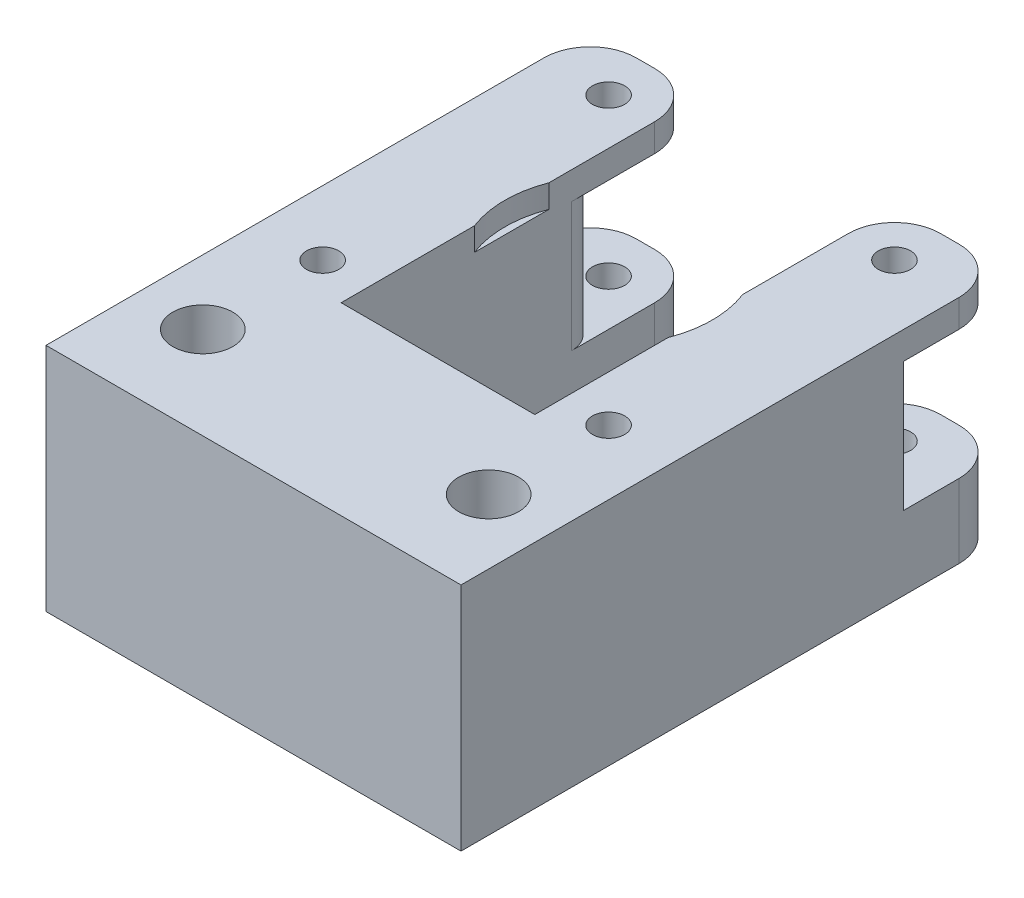
SolidWorks part; units mm, degrees
material "ABS"
ref_plane "Front Plane" through (0, 0, 0) normal (0, 0, 1) x (1, 0, 0)
ref_plane "Top Plane" through (0, 0, 0) normal (0, 1, 0) x (1, 0, 0)
ref_plane "Right Plane" through (0, 0, 0) normal (1, 0, 0) x (0, 0, -1)
sketch "Sketch1" plane through (0, 0, 0) normal (0, 1, 0) x (1, 0, 0)
  line L1 (-22.5, -10) -> (22.5, -10)
  line L2 (-22.5, -10) -> (-22.5, 10)
  line L3 (-22.5, 10) -> (22.5, 10)
  line L4 (22.5, -10) -> (22.5, 10)
  line L5 (-22.5, -10) -> (22.5, 10) construction
  line L6 (-22.5, 10) -> (22.5, -10) construction
  point P0 (0, 0)
  dimension "D1" = 20
  dimension "D2" = 45
extrude "Boss-Extrude1" add sketch "Sketch1" along normal blind 25
sketch "Sketch2" plane through (0, 0, -10) normal (0, 0, -1) x (-1, 0, 0)
  line L0 (-22.5, 25) -> (-22.5, 0) construction
  line L1 (-22.5, 25) -> (-10.5, 25)
  line L2 (-22.5, 25) -> (-22.5, 0)
  line L3 (-22.5, 0) -> (-10.5, 0)
  line L4 (-10.5, 25) -> (-10.5, 0)
  line L5 (-22.5, 25) -> (22.5, 25) construction
  line L11 (22.5, 25) -> (10.5, 25)
  line L12 (22.5, 25) -> (22.5, 0)
  line L13 (22.5, 0) -> (10.5, 0)
  line L14 (10.5, 25) -> (10.5, 0)
  dimension "D1" = 25
  dimension "D2" = 12
  dimension "D3" = 12
  dimension "D4" = 25
extrude "Boss-Extrude2" add sketch "Sketch2" along normal blind 40
sketch "Sketch3" plane through (0, 25, 0) normal (0, 1, 0) x (1, 0, 0)
  line L1 (22.5, -10) -> (22.5, 50) construction
  line L2 (10.5, 10) -> (-10.5, 10) construction
  circle A0 centre (15.5, 44) radius 1.75
  circle A1 centre (15.5, 13) radius 1.75
  circle A2 centre (-15.5, 13) radius 1.75
  circle A3 centre (-15.5, 44) radius 1.75
  dimension "D1" = 3.5
  dimension "D3" = 3.5
  dimension "D6" = 3.5
  dimension "D7" = 3.5
  dimension "D2" = 7
  dimension "D4" = 3
  dimension "D5" = 31
  dimension "D8" = 31
extrude "Cut-Extrude1" cut sketch "Sketch3" against normal through all
sketch "Sketch4" plane through (0, 25, 0) normal (0, 1, 0) x (1, 0, 0)
  line L0 (22.5, -10) -> (22.5, 50) construction
  line L1 (-22.5, 50) -> (-22.5, -10) construction
  circle A0 centre (-15.5, 0) radius 1.75
  circle A1 centre (15.5, 0) radius 1.75
  dimension "D1" = 3.5
  dimension "D2" = 3.5
  dimension "D3" = 7
  dimension "D4" = 7
extrude "Cut-Extrude2" cut sketch "Sketch4" against normal blind 25
hole_wizard "CBORE for M3 Hex Socket Head Cap Screw1" positions "Sketch5" profile "Sketch6" counterbore size "M3" standard "ISO" end condition through all
sketch "Sketch5" plane through (0, 25, 0) normal (0, 1, 0) x (1, 0, 0)
  point P0 (15.5, 0)
  point P3 (-15.5, 0)
sketch "Sketch6" plane through (15.5, 25, 0) normal (1, 0, 0) x (0, 0, 1)
  line L0 (0, 0) -> (0, 25)
  line L1 (0, 25) -> (1.75, 25)
  line L3 (1.75, 25) -> (1.75, 11.4)
  line L4 (1.75, 11.4) -> (3.25, 11.4)
  line L5 (3.25, 11.4) -> (3.25, 0)
  line L7 (3.25, 0) -> (0, 0)
  line L11 (0, -6.35) -> (0, 107.95) construction
  dimension "Thru Hole Dia." = 3.5
  dimension "Thru Hole Depth" = 25
  dimension "C'Bore Dia." = 6.5
  dimension "C'Bore Depth" = 11.4
hole_wizard "CBORE for M3 Hex Socket Head Cap Screw2" positions "Sketch7" profile "Sketch8" counterbore size "M3" standard "ISO" end condition through all
sketch "Sketch7" plane through (0, 0, 0) normal (0, -1, 0) x (-1, 0, 0)
  point P0 (15.5, 44)
  point P3 (15.5, 13)
  point P6 (-15.5, 13)
  point P9 (-15.5, 44)
sketch "Sketch8" plane through (-15.5, 0, -44) normal (1, 0, 0) x (0, 0, -1)
  line L0 (0, 0) -> (0, 25)
  line L1 (0, 25) -> (1.75, 25)
  line L3 (1.75, 25) -> (1.75, 4)
  line L4 (1.75, 4) -> (3.25, 4)
  line L5 (3.25, 4) -> (3.25, 0)
  line L7 (3.25, 0) -> (0, 0)
  line L11 (0, -6.35) -> (0, 107.95) construction
  dimension "Thru Hole Dia." = 3.5
  dimension "Thru Hole Depth" = 25
  dimension "C'Bore Dia." = 6.5
  dimension "C'Bore Depth" = 4
hole_wizard "CBORE for M3 Pan Head Screw1" positions "Sketch11" profile "Sketch12" counterbore size "M3" standard "JIS" end condition through all
sketch "Sketch11" plane through (0, 0, 0) normal (0, -1, 0) x (-1, 0, 0)
  point P0 (-15.5, 13)
  point P3 (15.5, 13)
sketch "Sketch12" plane through (15.5, 0, -13) normal (1, 0, 0) x (0, 0, -1)
  line L0 (0, 0) -> (0, 25)
  line L1 (0, 25) -> (1.75, 25)
  line L3 (1.75, 25) -> (1.75, 12.4)
  line L4 (1.75, 12.4) -> (3.25, 12.4)
  line L5 (3.25, 12.4) -> (3.25, 0)
  line L7 (3.25, 0) -> (0, 0)
  line L11 (0, -6.35) -> (0, 107.95) construction
  dimension "Thru Hole Dia." = 3.5
  dimension "Thru Hole Depth" = 25
  dimension "C'Bore Dia." = 6.5
  dimension "C'Bore Depth" = 12.4
sketch "Sketch9" plane through (22.5, 0, 0) normal (1, 0, 0) x (0, 0, -1)
  line L0 (50, 25) -> (50, 0) construction
  line L1 (50, 22) -> (38, 22)
  line L2 (50, 22) -> (50, 8)
  line L3 (50, 8) -> (38, 8)
  line L4 (38, 22) -> (38, 8)
  line L5 (-10, 25) -> (50, 25) construction
  line L6 (-10, 0) -> (50, 0) construction
  dimension "D1" = 12
  dimension "D2" = 3
  dimension "D3" = 8
extrude "Cut-Extrude3" cut sketch "Sketch9" against normal through all and the other way through all
sketch "Sketch10" plane through (0, 0, -50) normal (0, 0, -1) x (-1, 0, 0)
  line L0 (22.5, 22) -> (10.5, 22) construction
  line L1 (-22.5, 8) -> (-10.5, 8)
  line L2 (-22.5, 8) -> (-22.5, 0)
  line L3 (-22.5, 0) -> (-10.5, 0)
  line L4 (-10.5, 8) -> (-10.5, 0)
  line L5 (10.5, 8) -> (22.5, 8)
  line L6 (10.5, 8) -> (10.5, 0)
  line L7 (10.5, 0) -> (22.5, 0)
  line L8 (22.5, 8) -> (22.5, 0)
  line L9 (-22.5, 25) -> (-10.5, 25)
  line L10 (-22.5, 25) -> (-22.5, 22)
  line L11 (-22.5, 22) -> (-10.5, 22)
  line L12 (-10.5, 25) -> (-10.5, 22)
  line L13 (10.5, 25) -> (22.5, 25)
  line L14 (10.5, 25) -> (10.5, 22)
  line L15 (10.5, 22) -> (22.5, 22)
  line L16 (22.5, 25) -> (22.5, 22)
extrude "Cut-Extrude5" cut sketch "Sketch10" against normal blind 1
fillet "Fillet2" radius 5 8 edges at (-10.5, 4, -49) (10.5, 4, -49) (-10.5, 23.5, -49) (10.5, 23.5, -49) (-22.5, 23.5, -49) (-22.5, 4, -49) (22.5, 4, -49) (22.5, 23.5, -49)
fillet "Fillet5" radius 3 2 edges at (-10.5, 15, -38) (10.5, 15, -38)
sketch "Sketch13" plane through (0, 25, 0) normal (0, 1, 0) x (1, 0, 0)
  line L0 (-15.5, 13) -> (15.5, 44) construction
  circle A0 centre (0, 28.5) radius 11.25
  dimension "D1" = 22.5
extrude "Cut-Extrude6" cut sketch "Sketch13" against normal blind 2.5
